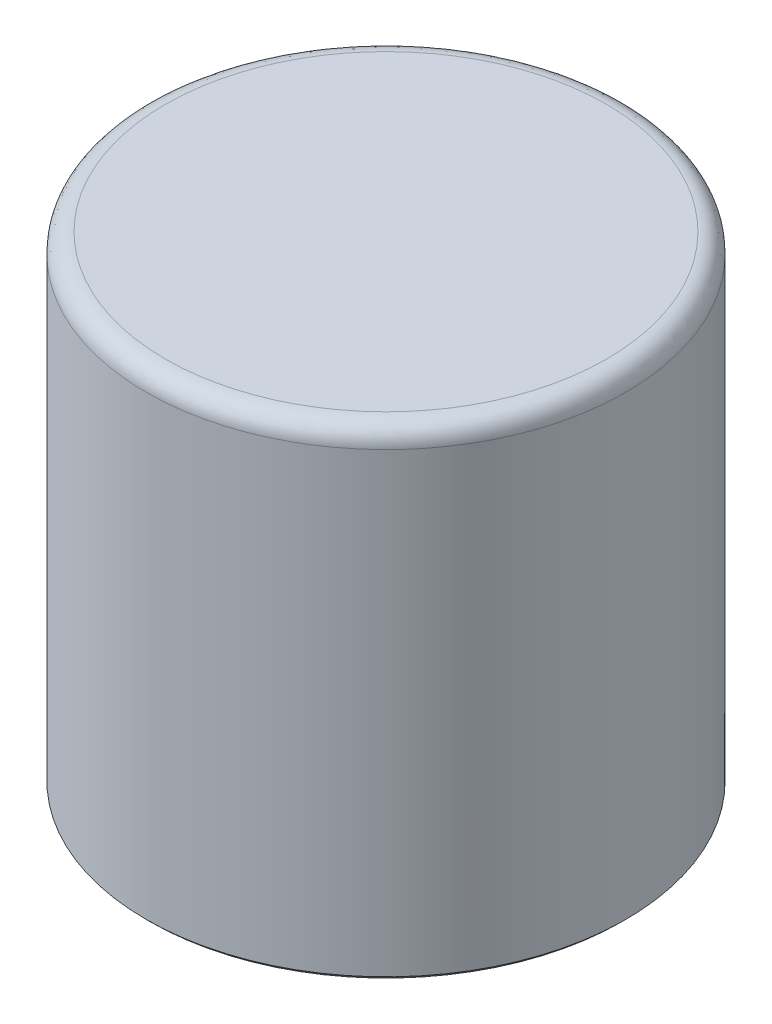
SolidWorks part; units mm, degrees
ref_plane "Front Plane" through (0, 0, 0) normal (0, 0, 1) x (1, 0, 0)
ref_plane "Top Plane" through (0, 0, 0) normal (0, 1, 0) x (1, 0, 0)
ref_plane "Right Plane" through (0, 0, 0) normal (1, 0, 0) x (0, 0, -1)
sketch "草图1" plane through (0, 0, 0) normal (0, 1, 0) x (1, 0, 0)
  circle A0 centre (0, 0) radius 12.5
  dimension "D1" = 25
extrude "凸台-拉伸1" add sketch "草图1" along normal blind 25
sketch "草图2" plane through (0, 0, 0) normal (0, -1, 0) x (1, 0, 0)
  circle A0 centre (0, 0) radius 10
  dimension "D1" = 20
extrude "切除-拉伸1" cut sketch "草图2" against normal blind 5
sketch "草图3" plane through (0, 5, 0) normal (0, -1, 0) x (1, 0, 0)
  circle A0 centre (0, 0) radius 3
  dimension "D1" = 6
extrude "切除-拉伸2" cut sketch "草图3" against normal blind 15
chamfer "倒角1" distance 0.2 angle 45 3 edges at (0, 5, -3) (0, 0, -10) (0, 0, 12.5)
fillet "圆角1" radius 1 1 edges at (0, 25, 12.5) conic rho 0.45
